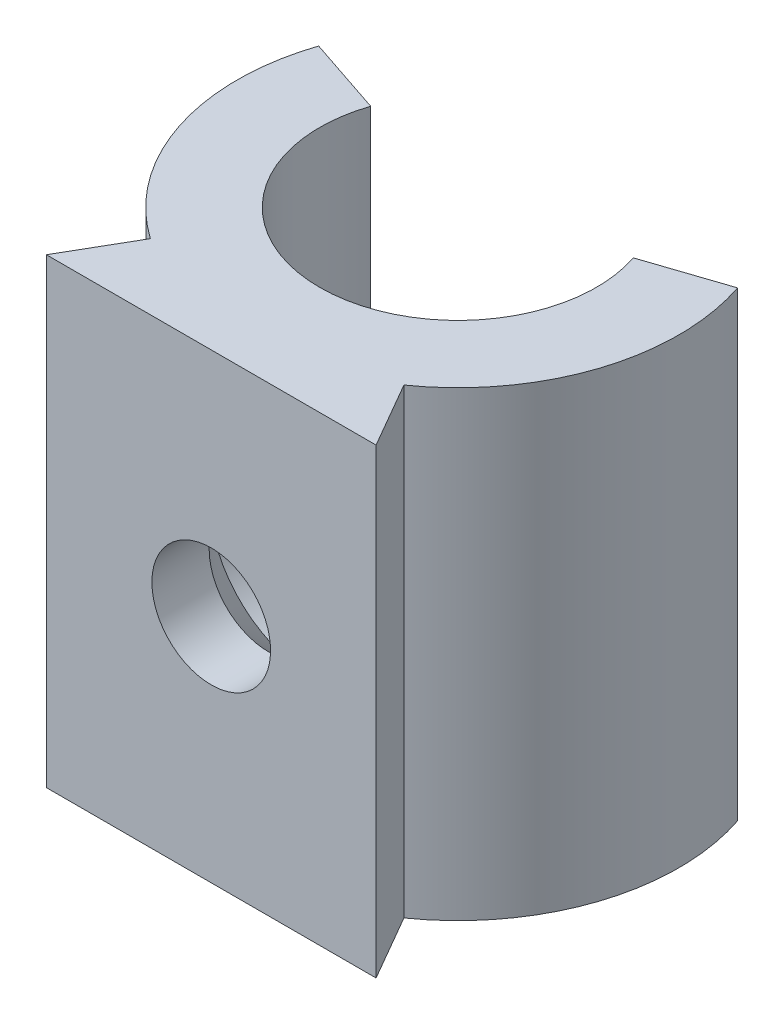
SolidWorks part; units mm, degrees
ref_plane "Front Plane" through (0, 0, 0) normal (0, 0, 1) x (1, 0, 0)
ref_plane "Top Plane" through (0, 0, 0) normal (0, 1, 0) x (1, 0, 0)
ref_plane "Right Plane" through (0, 0, 0) normal (1, 0, 0) x (0, 0, -1)
sketch "Sketch1" plane through (0, 0, 0) normal (0, 1, 0) x (1, 0, 0)
  line L0 (0, -1000) -> (0, 49000) construction
  line L1 (0, 0) -> (-6.3538, 2.1259)
  line L2 (0, 0) -> (6.3538, 2.1259)
  line L3 (-5, -7.4867) -> (5, -7.4867)
  line L4 (5, -7.4867) -> (3.8453, -5.4867)
  line L5 (-5, -7.4867) -> (-3.8453, -5.4867)
  circle A0 centre (0, 0) radius 4.2
  circle A1 centre (0, 0) radius 6.7
  point P12 (0, -7.4867)
  dimension "D1" = 8.4
  dimension "D3" = 143
  dimension "D4" = 2
  dimension "D5" = 10
  dimension "D6" = 60
  dimension "D2" = 2.5
extrude "Boss-Extrude1" add sketch "Sketch1" along normal blind 14 contours A1 L0 A0 L1 | L0 A1 L2 A0 | L0 L3 L4 A1 | L3 L0 A1 L5 region at (-2.6502, 0, 6.84) region at (2.6502, 0, 6.84) region at (-3.8577, 0, 2.7771) region at (3.8577, 0, 2.7771)
ref_plane "Plane1" through (0, 0, 4.2) normal (0, 0, -1) x (-1, 0, 0)
sketch "Sketch4" plane through (0, 0, 4.2) normal (0, 0, -1) x (-1, 0, 0)
  line L2 (4.2, 14) -> (-4.2, 14) construction
  line L4 (4.2, 14) -> (-4.2, 14) construction
  line L5 (-4.2, 0) -> (4.2, 0) construction
  line L6 (-4.2, 0) -> (4.2, 0) construction
  line L7 (0, 14) -> (0, 0) construction
  circle A0 centre (0, 7) radius 3.25
  dimension "D1" = 6.5
extrude "Cut-Extrude1" cut sketch "Sketch4" along normal through all and the other way blind 0.2 contours A0
hole_wizard "CSK for M3 Flat Head Machine Screw4" positions "Sketch7" profile "Sketch8" countersink size "M3" standard "ANSI Metric"
sketch "Sketch7" plane through (0, 0, 4.4) normal (0, 0, -1) x (-1, 0, 0)
  point P0 (0, 7)
sketch "Sketch8" plane through (0, 7, 4.4) normal (1, 0, 0) x (0, 1, 0)
  line L0 (0, 0) -> (0, 8.5815)
  line L1 (0, 8.5815) -> (1.8, 7.5)
  line L2 (1.8, 7.5) -> (1.8, 1.35)
  line L3 (1.8, 1.35) -> (3.15, 0)
  line L5 (3.15, 0) -> (0, 0)
  line L6 (-1.8, 1.35) -> (-3.15, 0) construction
  line L10 (0, 8.5815) -> (-1.8, 7.5) construction
  line L11 (0, -6.35) -> (0, 107.95) construction
  dimension "Hole Dia." = 3.6
  dimension "Hole Depth" = 7.5
  dimension "Near C'Sink Dia." = 6.3
  dimension "Near C'Sink Angle" = 90
  dimension "Drill Angle" = 118
